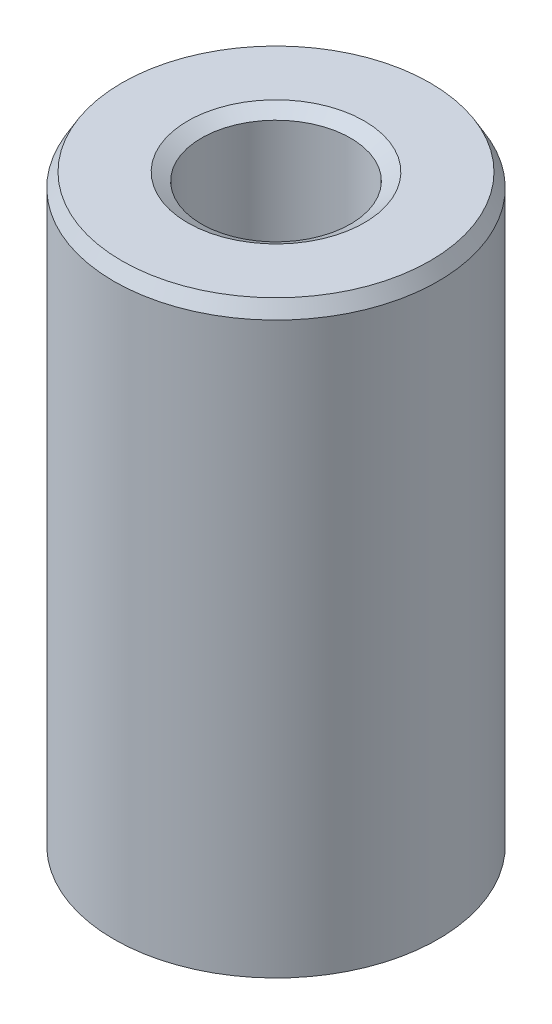
SolidWorks part; units mm, degrees
ref_plane "Front Plane" through (0, 0, 0) normal (0, 0, 1) x (1, 0, 0)
ref_plane "Top Plane" through (0, 0, 0) normal (0, 1, 0) x (1, 0, 0)
ref_plane "Right Plane" through (0, 0, 0) normal (1, 0, 0) x (0, 0, -1)
sketch "Sketch1" plane through (0, 0, 0) normal (0, 1, 0) x (1, 0, 0)
  circle A0 centre (0, 0) radius 35
  dimension "SLEEVE_OD" = 70
extrude "Boss-Extrude1" add sketch "Sketch1" along normal blind 127.7039
sketch "Sketch2" plane through (0, 0, 0) normal (0, 1, 0) x (1, 0, 0)
  circle A0 centre (0, 0) radius 16.0941
  dimension "BORE_D" = 32.1882
extrude "Cut-Extrude1" cut sketch "Sketch2" along normal through all
chamfer "Chamfer1" distance 2.9709 angle 30 4 edges at (0, 127.7039, 16.0941) (0, 0, 16.0941) (0, 0, 35) (0, 127.7039, 35) first distance on face at (0, 127.7039, 16.0941) first distance on face at (0, 0, 16.0941) first distance on face at (0, 127.7039, 35)
